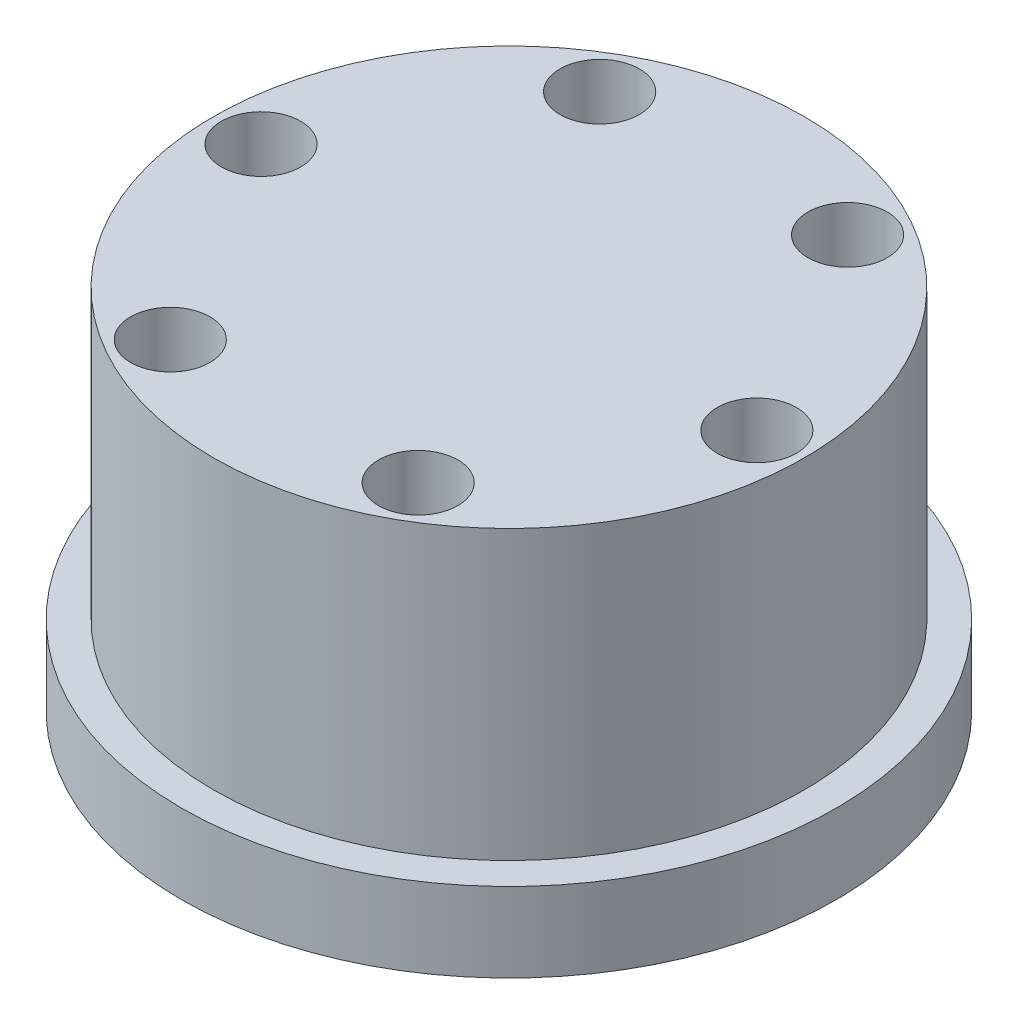
SolidWorks part; units mm, degrees
ref_plane "Front Plane" through (0, 0, 0) normal (0, 0, 1) x (1, 0, 0)
ref_plane "Top Plane" through (0, 0, 0) normal (0, 1, 0) x (1, 0, 0)
ref_plane "Right Plane" through (0, 0, 0) normal (1, 0, 0) x (0, 0, -1)
sketch "Sketch1" plane through (0, 0, 0) normal (0, 1, 0) x (1, 0, 0)
  circle A0 centre (0, 0) radius 16.5
  circle A1 centre (0, 0) radius 12.5 construction
  circle A2 centre (0, 12.5) radius 1.5
  circle A3 centre (10.8253, 6.25) radius 1.5
  circle A4 centre (10.8253, -6.25) radius 1.5
  circle A5 centre (0, -12.5) radius 1.5
  circle A6 centre (-10.8253, -6.25) radius 1.5
  circle A7 centre (-10.8253, 6.25) radius 1.5
  point P19 (0, 0)
  dimension "D1" = 33
  dimension "D2" = 25
  dimension "D3" = 3
  dimension "D4" = 6
extrude "Boss-Extrude1" add sketch "Sketch1" along normal blind 4
sketch "Sketch2" plane through (0, 4, 0) normal (0, 1, 0) x (1, 0, 0)
  circle A0 centre (0, 0) radius 14.9
  dimension "D1" = 29.8
extrude "Boss-Extrude2" add sketch "Sketch2" along normal blind 14.5
sketch "Sketch3" plane through (0, 0, 0) normal (0, -1, 0) x (1, 0, 0)
  circle A0 centre (0, 0) radius 9
  dimension "D1" = 18
extrude "Cut-Extrude1" cut sketch "Sketch3" against normal blind 2
sketch "Sketch4" plane through (0, 2, 0) normal (0, -1, 0) x (1, 0, 0)
  circle A0 centre (0, 0) radius 6.6
  dimension "D1" = 13.2
extrude "Cut-Extrude2" cut sketch "Sketch4" against normal blind 4
sketch "Sketch5" plane through (0, 18.5, 0) normal (0, 1, 0) x (1, 0, 0)
  circle A0 centre (0, 0) radius 12.5 construction
  circle A1 centre (-12.5, 0) radius 2
  circle A2 centre (-6.25, 10.8253) radius 2
  circle A3 centre (6.25, 10.8253) radius 2
  circle A4 centre (12.5, 0) radius 2
  circle A5 centre (6.25, -10.8253) radius 2
  circle A6 centre (-6.25, -10.8253) radius 2
  point P17 (0, 0)
  dimension "D1" = 25
  dimension "D2" = 4
  dimension "D3" = 6
extrude "Cut-Extrude3" cut sketch "Sketch5" against normal blind 6.5
